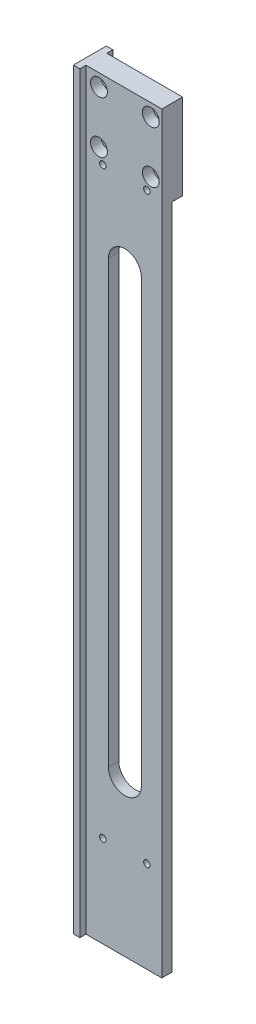
SolidWorks part; units mm, degrees
note: The reader was unsure of these and kept them because the rebuilt part matched: shared geometry of "Sketch1<3>", "Sketch1<6>".
material "6061-T6 (SS)"
ref_plane "Front Plane" through (0, 0, 0) normal (0, 0, 1) x (1, 0, 0)
ref_plane "Top Plane" through (0, 0, 0) normal (0, 1, 0) x (1, 0, 0)
ref_plane "Right Plane" through (0, 0, 0) normal (1, 0, 0) x (0, 0, -1)
sketch "Sketch1" plane through (0, 0, 0) normal (0, 0, 1) x (1, 0, 0)
  line L0 (0, 0) -> (0, 19.896) construction
  line L1 (-15, -145.15) -> (15, -145.15)
  line L2 (-15, -145.15) -> (-15, 145.15)
  line L3 (-15, 145.15) -> (15, 145.15)
  line L4 (15, -145.15) -> (15, 145.15)
  line L5 (-15, -145.15) -> (15, 145.15) construction
  line L6 (-15, 145.15) -> (15, -145.15) construction
  line L7 (-15, 145.15) -> (-17.5, 145.15)
  line L8 (-15, 145.15) -> (-15, -145.15)
  line L9 (-15, -145.15) -> (-17.5, -145.15)
  line L10 (-17.5, 145.15) -> (-17.5, -145.15)
  line L12 (15, 145.15) -> (15, -54.85)
  line L13 (-10, 140.35) -> (10, 140.35) construction
  line L14 (-10, 140.35) -> (-10, 120.35) construction
  line L15 (-10, 120.35) -> (10, 120.35) construction
  line L16 (10, 140.35) -> (10, 120.35) construction
  point P0 (0, 0)
  dimension "D1" = 290.3
  dimension "D2" = 30
  dimension "D3" = 2.5
  dimension "D4" = 20
  dimension "D5" = 20
  dimension "D6" = 4.8
extrude "Boss-Extrude1" add sketch "Sketch1" along normal blind 8
extrude "Boss-Extrude2" add sketch "Sketch1<3>" along normal offset from surface (10.35 mm away) 2.35 contours L7 L10 L9 L2 | L12
sketch "Sketch1<3>" plane through (0, 0, 0) normal (0, 0, 1) x (1, 0, 0) same geometry as "Sketch1"
extrude "Boss-Extrude3" add sketch "Sketch1<6>" against normal blind 2.35 contours L7 L10 L9 L2
sketch "Sketch1<6>" plane through (0, 0, 0) normal (0, 0, 1) x (1, 0, 0) same geometry as "Sketch1"
hole_wizard "CBORE for M3 SHCS1" positions "Sketch6" profile "Sketch5" counterbore size "M3" standard "ANSI Metric" end condition through all
sketch "Sketch6" plane through (0, 0, 8) normal (0, 0, 1) x (1, 0, 0)
  point P0 (-10, 140.35)
  point P3 (10, 140.35)
  point P6 (10, 120.35)
  point P9 (-10, 120.35)
sketch "Sketch5" plane through (-10, 140.35, 8) normal (1, 0, 0) x (0, -1, 0)
  line L0 (0, 0) -> (0, 10.35)
  line L1 (0, 10.35) -> (1.8, 10.35)
  line L3 (1.8, 10.35) -> (1.8, 4)
  line L4 (1.8, 4) -> (3.25, 4)
  line L5 (3.25, 4) -> (3.25, 0)
  line L7 (3.25, 0) -> (0, 0)
  line L11 (0, -6.35) -> (0, 107.95) construction
  dimension "Thru Hole Dia." = 3.6
  dimension "Thru Hole Depth" = 10.35
  dimension "C'Bore Dia." = 6.5
  dimension "C'Bore Depth" = 4
hole_wizard "M3x0.5 Tapped Hole1" positions "Sketch9" profile "Sketch10" tap size "M3x0.5" standard "ANSI Metric" end condition through all
sketch "Sketch9" plane through (0, 0, 8) normal (0, 0, 1) x (1, 0, 0)
  line L1 (0, 0) -> (0, 22.5374) construction
  line L4 (-15, 145.15) -> (15, 145.15) construction
  point P0 (-8.5, 115.15)
  point P2 (8.5, 115.15)
  point P4 (8.5, -109.85)
  point P6 (-8.5, -109.85)
  dimension "D1" = 225
  dimension "D2" = 17
  dimension "D3" = 30
sketch "Sketch10" plane through (-8.5, 115.15, 8) normal (1, 0, 0) x (0, -1, 0)
  line L0 (0, 0) -> (0, 10.35)
  line L1 (0, 10.35) -> (1.25, 10.35)
  line L2 (1.25, 10.35) -> (1.25, 0)
  line L5 (1.25, 0) -> (0, 0)
  line L11 (0, -6.35) -> (0, 107.95) construction
  dimension "Thru Tap Drill Dia." = 2.5
  dimension "Thru Tap Drill Depth" = 10.35
cosmetic thread "Hole Thread9" parameters "D2"=3
cosmetic thread "Hole Thread10" parameters "D2"=3
cosmetic thread "Hole Thread11" parameters "D2"=3
cosmetic thread "Hole Thread12" parameters "D2"=3
sketch "Sketch11" plane through (0, 0, 8) normal (0, 0, 1) x (1, 0, 0)
  line L0 (0, -85) -> (0, 85) construction
  line L1 (-6.35, -85) -> (-6.35, 85)
  line L2 (6.35, -85) -> (6.35, 85)
  arc A0 (-6.35, -85) -> (6.35, -85) centre (0, -85) ccw
  arc A1 (6.35, 85) -> (-6.35, 85) centre (0, 85) ccw
  point P2 (0, 0)
  dimension "D1" = 6.35
  dimension "D2" = 170
extrude "Cut-Extrude1" cut sketch "Sketch11" against normal blind 10
sketch "Sketch12" plane through (0, 0, 8) normal (0, 0, 1) x (1, 0, 0)
  line L0 (-15, -145.15) -> (15, -145.15) construction
  line L1 (15, 145.15) -> (14.25, 145.15)
  line L2 (15, 145.15) -> (15, -145.15)
  line L3 (15, -145.15) -> (14.25, -145.15)
  line L4 (14.25, 145.15) -> (14.25, -145.15)
  dimension "D1" = 0.75
extrude "Cut-Extrude2" cut sketch "Sketch12" against normal through all contours L4 L3 L2 L1
sketch "Sketch15" plane through (0, 0, 0) normal (0, 0, -1) x (-1, 0, 0)
  line L0 (17.5, 145.15) -> (17.5, -145.15) construction
  line L1 (-14.25, -145.15) -> (17.5, -145.15)
  line L2 (-14.25, -145.15) -> (-14.25, 112.15)
  line L3 (-14.25, 112.15) -> (17.5, 112.15)
  line L4 (17.5, -145.15) -> (17.5, 112.15)
  line L5 (15, 145.15) -> (-14.25, 145.15) construction
  dimension "D1" = 33
extrude "Cut-Extrude3" cut sketch "Sketch15" against normal blind 4 and the other way up to surface contours L3 L4 L1 L2 other way up to face at (-16.25, 0, -2.35)
